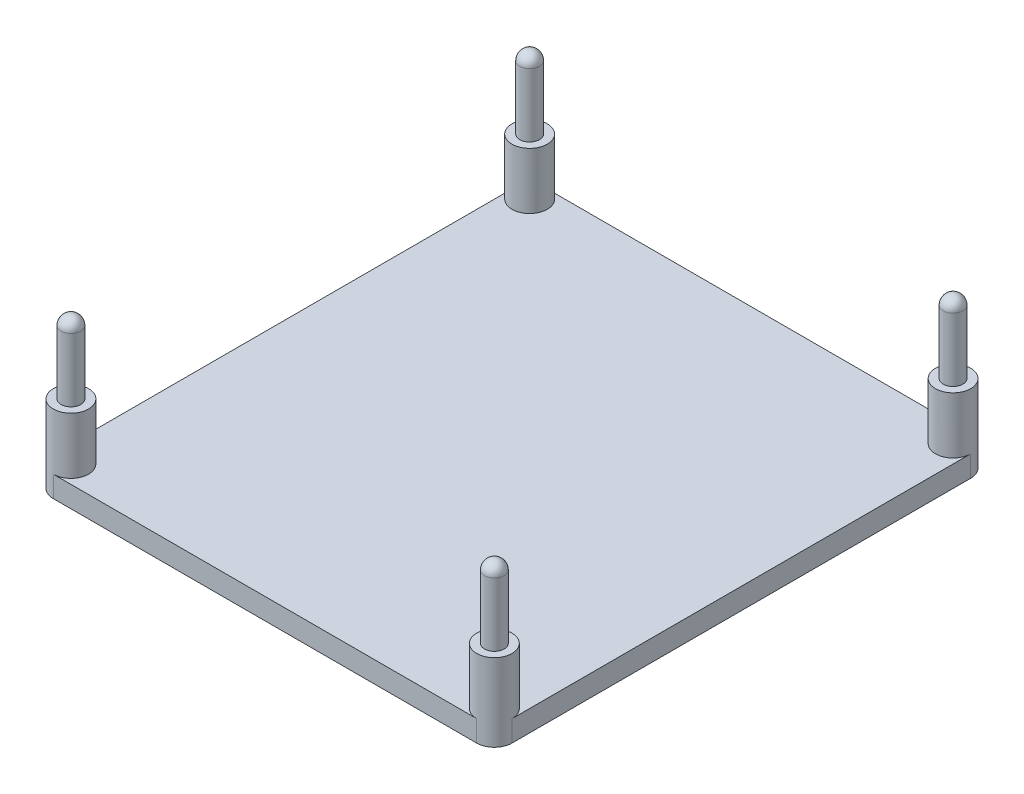
SolidWorks part; units mm, degrees
ref_plane "Front Plane" through (0, 0, 0) normal (0, 0, 1) x (1, 0, 0)
ref_plane "Top Plane" through (0, 0, 0) normal (0, 1, 0) x (1, 0, 0)
ref_plane "Right Plane" through (0, 0, 0) normal (1, 0, 0) x (0, 0, -1)
sketch "Sketch1" plane through (0, 0, 0) normal (0, 1, 0) x (1, 0, 0)
  line L0 (0, -44.45) -> (0, 44.45) construction
  line L1 (-41.275, 44.45) -> (41.275, 44.45)
  line L2 (-41.275, 44.45) -> (-41.275, -44.45)
  line L3 (-41.275, -44.45) -> (41.275, -44.45)
  line L4 (41.275, 44.45) -> (41.275, -44.45)
  line L5 (-41.275, 44.45) -> (41.275, -44.45) construction
  line L6 (-41.275, -44.45) -> (41.275, 44.45) construction
  line L7 (-41.275, 0) -> (41.275, 0) construction
  circle A0 centre (38.1, -41.275) radius 2.3812
  circle A1 centre (-38.1, -41.275) radius 2.3812
  circle A2 centre (38.1, 41.275) radius 2.3812
  circle A3 centre (-38.1, 41.275) radius 2.3812
  point P0 (0, 0)
  dimension "D3" = 76.2
  dimension "D5" = 38.1
  dimension "D6" = 3.175
  dimension "D1" = 88.9
  dimension "D2" = 82.55
  dimension "D4" = 82.55
sketch "Sketch2" plane through (0, 0, 0) normal (0, 1, 0) x (1, 0, 0)
  line L0 (0, -44.45) -> (0, 44.45) construction
  line L1 (-41.275, 44.45) -> (41.275, 44.45)
  line L2 (-41.275, 44.45) -> (-41.275, -44.45)
  line L3 (-41.275, -44.45) -> (41.275, -44.45)
  line L4 (41.275, 44.45) -> (41.275, -44.45)
  line L5 (-41.275, 44.45) -> (41.275, -44.45) construction
  line L6 (-41.275, -44.45) -> (41.275, 44.45) construction
  line L7 (-41.275, 0) -> (41.275, 0) construction
  circle A0 centre (38.1, -41.275) radius 1.778
  circle A1 centre (-38.1, -41.275) radius 1.778
  circle A2 centre (38.1, 41.275) radius 1.778
  circle A3 centre (-38.1, 41.275) radius 1.778
  circle A4 centre (-38.1, 41.275) radius 3.175
  circle A5 centre (38.1, 41.275) radius 3.175
  circle A6 centre (38.1, -41.275) radius 3.175
  circle A7 centre (-38.1, -41.275) radius 3.175
  point P0 (0, 0)
  dimension "D3" = 76.2
  dimension "D5" = 38.1
  dimension "D6" = 3.175
  dimension "D7" = 2
  dimension "D9" = 3.556
  dimension "D10" = 3.556
  dimension "D11" = 3.556
  dimension "D12" = 3.556
  dimension "D1" = 88.9
  dimension "D2" = 82.55
  dimension "D4" = 82.55
  dimension "D13" = 3.175
  dimension "D14" = 3.175
  dimension "D15" = 3.175
  dimension "D16" = 3.175
  dimension "D17" = 3.175
  dimension "D18" = 3.175
  dimension "D8" = 2
extrude "Boss-Extrude2" add sketch "Sketch2" along normal blind 25.4 contours A2 | A3 | A1 | A0
extrude "Boss-Extrude3" add sketch "Sketch2<4>" along normal blind 13.97 contours A7 | A6 | A5 | A4
sketch "Sketch2<4>" plane through (0, 0, 0) normal (0, 1, 0) x (1, 0, 0) same geometry as "Sketch2"
extrude "Boss-Extrude4" add sketch "Sketch2<5>" along normal blind 3.81 contours A7 L3 A6 L4 A5 L1 A4 L2 region at (0, 0, 0)
sketch "Sketch2<5>" plane through (0, 0, 0) normal (0, 1, 0) x (1, 0, 0) same geometry as "Sketch2"
sketch "Sketch3" plane through (0, 25.4, 0) normal (0, 1, 0) x (1, 0, 0)
  line L0 (38.1, -39.497) -> (38.1, -43.053) construction
  line L1 (38.1, -39.497) -> (38.1, -43.053)
  circle A0 centre (38.1, -41.275) radius 1.778 construction
  circle A1 centre (38.1, -41.275) radius 1.778 construction
  arc A2 (38.1, -43.053) -> (38.1, -39.497) centre (38.1, -41.275) ccw
revolve "Revolve1" add sketch "Sketch3" angle 180 about L0
pattern_linear "LPattern1" count 2 spacing 82.55 along (0, 0, -1) count 2 spacing 76.2 along (-1, 0, 0) of "Revolve1"
